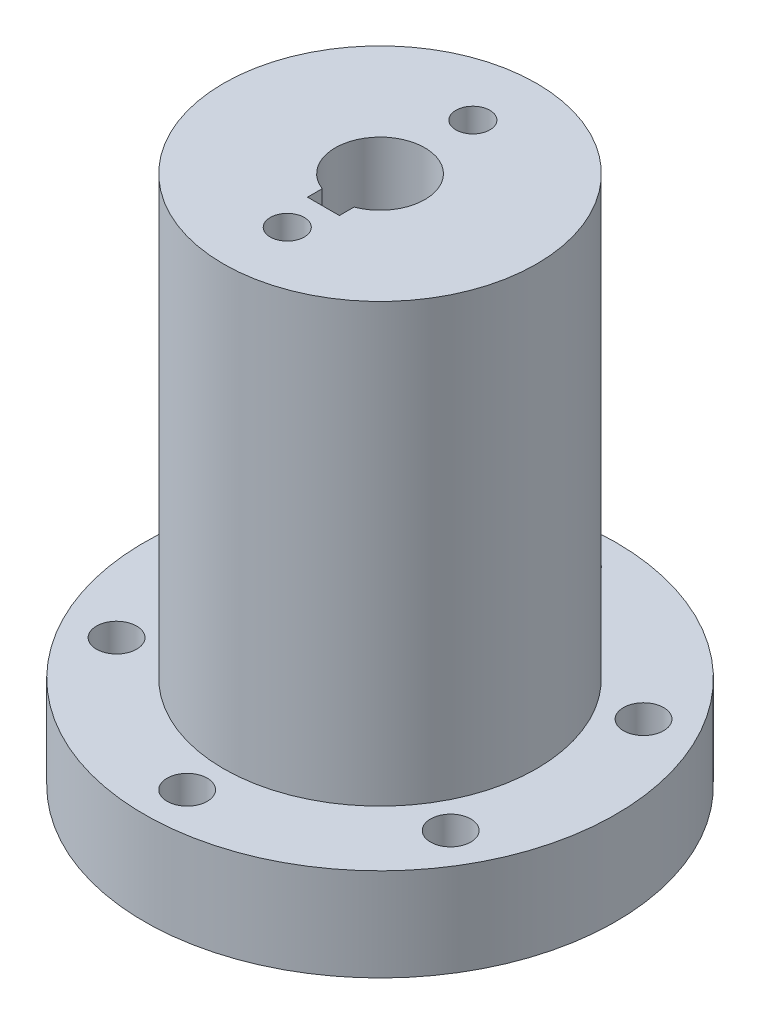
SolidWorks part; units mm, degrees
ref_plane "Front Plane" through (0, 0, 0) normal (0, 0, 1) x (1, 0, 0)
ref_plane "Top Plane" through (0, 0, 0) normal (0, 1, 0) x (1, 0, 0)
ref_plane "Right Plane" through (0, 0, 0) normal (1, 0, 0) x (0, 0, -1)
sketch "Sketch1" plane through (0, 0, 0) normal (0, 1, 0) x (1, 0, 0)
  circle A0 centre (0, 0) radius 25.3
extrude "Boss-Extrude1" add sketch "Sketch1" along normal blind 8.5
sketch "Sketch2" plane through (0, 8.5, 0) normal (0, 1, 0) x (1, 0, 0)
  circle A0 centre (0, 0) radius 25.3
extrude "Boss-Extrude2" add sketch "Sketch2" along normal blind 57.15
sketch "Sketch7" plane through (0, 65.65, 0) normal (0, 1, 0) x (1, 0, 0)
  circle A0 centre (0, 0) radius 25.3
extrude "Boss-Extrude4" add sketch "Sketch7" along normal blind 15
sketch "Sketch5" plane through (0, 0, 0) normal (0, -1, 0) x (1, 0, 0)
  line L1 (-2.575, 9.15) -> (2.575, 9.15)
  line L2 (-2.575, 9.15) -> (-2.575, 4)
  line L3 (-2.575, 4) -> (2.575, 4)
  line L4 (2.575, 9.15) -> (2.575, 4)
  circle A0 centre (0, 0) radius 7.25
  dimension "D1" = 5.15
  dimension "D2" = 5.15
  dimension "D3" = 9.15
  dimension "D4" = 2.575
extrude "Cut-Extrude3" cut sketch "Sketch5" against normal blind 115 contours L2 A0 L4 L3 | L4 A0 L2 L3 | A0 L4 L1 L2 region at (0, 0, 8.1175) region at (0, 0, 5.5505) region at (0, 0, -0.5929)
sketch "Sketch6" plane through (0, 0, 0) normal (0, -1, 0) x (1, 0, 0)
  circle A0 centre (0, 0) radius 38.1
extrude "Boss-Extrude3" add sketch "Sketch6" along normal blind 15
sketch "Sketch9" plane through (0, 0, 0) normal (0, 1, 0) x (1, 0, 0)
  line L1 (0, 31.1769) -> (-27, 15.5885)
  line L2 (-27, 15.5885) -> (-27, -15.5885)
  line L3 (-27, -15.5885) -> (0, -31.1769)
  line L4 (0, -31.1769) -> (27, -15.5885)
  line L5 (27, -15.5885) -> (27, 15.5885)
  line L6 (27, 15.5885) -> (0, 31.1769)
  circle A0 centre (0, 0) radius 27 construction
  circle A1 centre (0, 31.1769) radius 3.25
  circle A2 centre (-27, 15.5885) radius 3.25
  circle A3 centre (-27, -15.5885) radius 3.25
  circle A4 centre (0, -31.1769) radius 3.25
  circle A5 centre (27, -15.5885) radius 3.25
  circle A6 centre (27, 15.5885) radius 3.25
extrude "Cut-Extrude4" cut sketch "Sketch9" against normal blind 20 contours L1 A2 L2 | L2 A2 L1 | L6 A1 L1 | L1 A1 L6 | L5 A6 L6 | L6 A6 L5 | L4 A5 L5 | L5 A5 L4 | L3 A4 L4 | L4 A4 L3 | L2 A3 L3 | L3 A3 L2 region at (0, 0, -29.3851) region at (0, 0, -32.0728) region at (-25.4482, 0, -14.6925) region at (-27.7759, 0, -16.0364) region at (27.7759, 0, -16.0364) region at (25.4482, 0, -14.6925) region at (-25.4482, 0, 14.6925) region at (-27.7759, 0, 16.0364) region at (27.7759, 0, 16.0364) region at (25.4482, 0, 14.6925) region at (0, 0, 29.3851) region at (0, 0, 32.0728)
sketch "Sketch10" plane through (0, 80.65, 0) normal (0, 1, 0) x (1, 0, 0)
  circle A0 centre (0, 15) radius 2.75
  circle A1 centre (0, -15) radius 2.75
  arc A2 (2.575, -6.7773) -> (-2.575, -6.7773) centre (0, 0) ccw construction
  dimension "D1" = 15
  dimension "D2" = 15
extrude "Cut-Extrude6" cut sketch "Sketch10" against normal blind 129
sketch "Sketch11" plane through (0, 80.65, 0) normal (0, 1, 0) x (1, 0, 0)
  line L0 (-2.575, -6.7773) -> (-2.575, -9.15)
  line L1 (-2.575, -9.15) -> (2.575, -9.15)
  line L2 (2.575, -9.15) -> (2.575, -6.7773)
  circle A0 centre (0, 0) radius 7.25
  arc M3 (-2.575, -6.7773) -> (2.575, -6.7773) centre (0, 0) cw
  line M4 (2.575, -6.7773) -> (2.575, -9.15)
  line M5 (2.575, -9.15) -> (-2.575, -9.15)
  line M6 (-2.575, -9.15) -> (-2.575, -6.7773)
extrude "Boss-Extrude5" add sketch "Sketch11" against normal blind 93 contours A0 M3 | A0 M6 M5 M4 region at (0, 80.65, 8.1175) region at (0, 80.65, 0)
extrude "Cut-Extrude7" cut sketch "Sketch11<3>" against normal blind 40 contours A0 M3 | A0 M6 M5 M4 region at (0, 80.65, 8.1175) region at (0, 80.65, 0)
sketch "Sketch11<3>" plane through (0, 80.65, 0) normal (0, 1, 0) x (1, 0, 0) same geometry as "Sketch11"
sketch "Sketch12" plane through (0, 80.65, 0) normal (0, 1, 0) x (1, 0, 0)
  circle A0 centre (0, 0) radius 25.3
extrude "Cut-Extrude8" cut sketch "Sketch12" against normal blind 10
